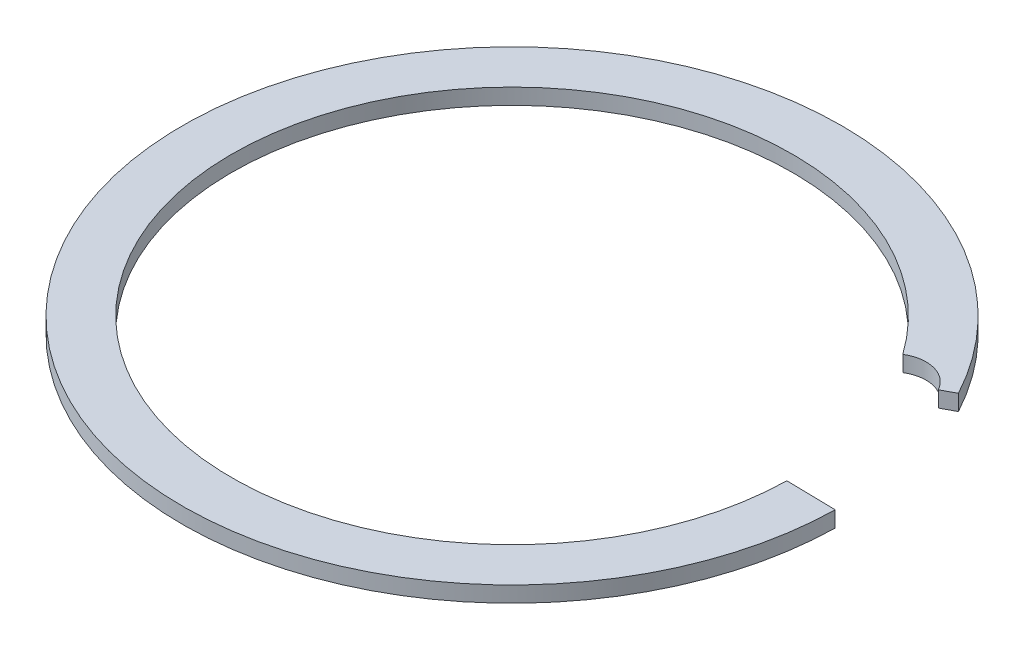
SolidWorks part; units mm, degrees
ref_plane "Front Plane" through (0, 0, 0) normal (0, 0, 1) x (1, 0, 0)
ref_plane "Top Plane" through (0, 0, 0) normal (0, 1, 0) x (1, 0, 0)
ref_plane "Right Plane" through (0, 0, 0) normal (1, 0, 0) x (0, 0, -1)
sketch "Sketch1" plane through (0, 0, 0) normal (0, 1, 0) x (1, 0, 0)
  circle A0 centre (0, 0) radius 10.5 construction
  arc A1 (9.7129, 5.227) -> (11.0279, -0.2127) centre (0, 0) ccw
  dimension "D1" = 21
  dimension "D2" = 11.03
extrude "Extrude-Thin1" add sketch "Sketch1" along normal blind 0.53 thin thin type one direction reverse wall 1.65
sketch "Sketch2" plane through (0, 0, 0) normal (0, 1, 0) x (1, 0, 0)
  circle A0 centre (8.2599, 4.4451) radius 1.1515
extrude "Cut-Extrude1" cut sketch "Sketch2" along normal through all
ref_axis "Axis1" through (0, 0, 0) along (0, 1, 0)
